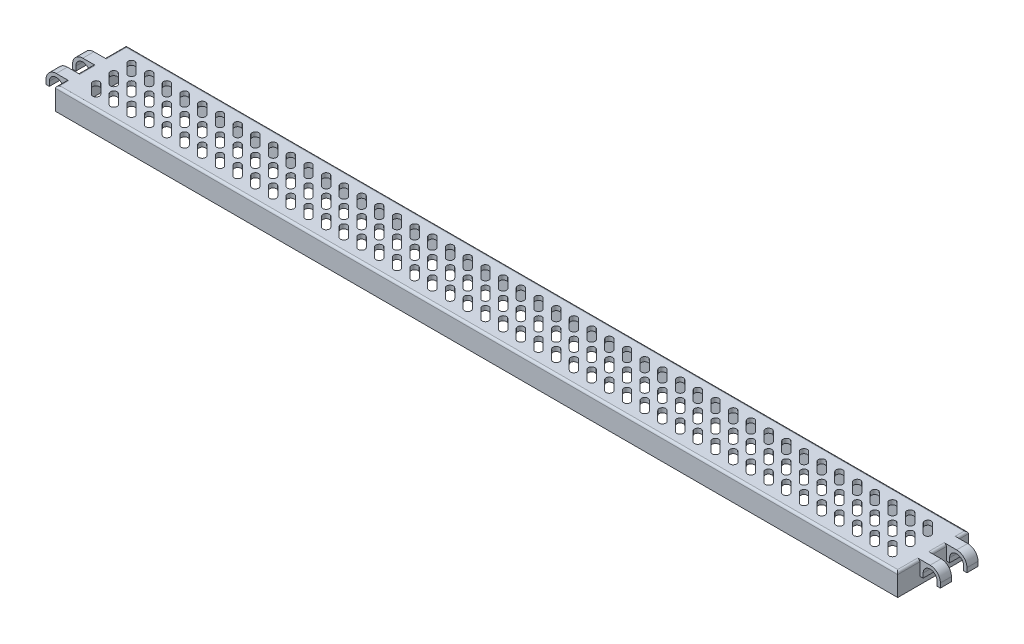
SolidWorks part; units mm, degrees
ref_plane "Ebene vorne" through (0, 0, 0) normal (0, 0, 1) x (1, 0, 0)
ref_plane "Ebene oben" through (0, 0, 0) normal (0, 1, 0) x (1, 0, 0)
ref_plane "Ebene rechts" through (0, 0, 0) normal (1, 0, 0) x (0, 0, -1)
sketch "Skizze1" plane through (0, 0, 0) normal (0, 0, 1) x (1, 0, 0)
  line L0 (-195, 0) -> (195, 0) construction
  line L1 (-198.15, 0) -> (-198.15, -2)
  line L2 (-191.85, 0) -> (-191.85, -2)
  line L3 (-190.35, -5.35) -> (190.35, -5.35)
  line L4 (-198.15, -2) -> (-199.65, -2)
  line L5 (-199.65, -2) -> (-199.65, 0)
  line L6 (-195, 4.65) -> (195, 4.65)
  line L7 (0, 4.65) -> (0, -5.35) construction
  line L8 (-191.85, -2) -> (-190.35, -2)
  line L9 (-190.35, -2) -> (-190.35, -5.35)
  line L10 (190.35, -2) -> (190.35, -5.35)
  line L11 (191.85, -2) -> (190.35, -2)
  line L12 (199.65, -2) -> (199.65, 0)
  line L13 (198.15, -2) -> (199.65, -2)
  line L14 (191.85, 0) -> (191.85, -2)
  line L15 (198.15, 0) -> (198.15, -2)
  arc A0 (-198.15, 0) -> (-191.85, 0) centre (-195, 0) cw
  arc A1 (-199.65, 0) -> (-195, 4.65) centre (-195, 0) cw
  arc A2 (199.65, 0) -> (195, 4.65) centre (195, 0) ccw
  arc A3 (198.15, 0) -> (191.85, 0) centre (195, 0) ccw
  point P3 (0, 0)
  dimension "D2" = 3.15
  dimension "D1" = 390
  dimension "D3" = 1.5
  dimension "D4" = 2
  dimension "D5" = 10
extrude "Aufsatz-Linear austragen2" add sketch "Skizze1" along normal mid plane 32
sketch "Skizze3" plane through (0, -5.35, 0) normal (0, -1, 0) x (1, 0, 0)
  line L0 (-190.35, 16) -> (-190.35, -16) construction
  line L1 (-199.65, 16) -> (-190.35, 16)
  line L2 (-199.65, 16) -> (-199.65, 11)
  line L3 (-199.65, 11) -> (-190.35, 11)
  line L4 (-190.35, 16) -> (-190.35, 11)
  line L5 (-199.65, 16) -> (-199.65, -16) construction
  line L6 (-199.65, 6) -> (-190.35, 6)
  line L7 (-199.65, 6) -> (-199.65, -1)
  line L8 (-199.65, -1) -> (-190.35, -1)
  line L9 (-190.35, 6) -> (-190.35, -1)
  line L10 (-190.35, 16) -> (-190.35, -16) construction
  line L11 (199.65, 16) -> (199.65, -16) construction
  line L12 (-199.65, -16) -> (-190.35, -16)
  line L13 (-199.65, -16) -> (-199.65, -6)
  line L14 (-199.65, -6) -> (-190.35, -6)
  line L15 (-190.35, -16) -> (-190.35, -6)
  line L16 (190.35, 16) -> (199.65, 16)
  line L17 (190.35, 16) -> (190.35, 6)
  line L18 (190.35, 6) -> (199.65, 6)
  line L19 (199.65, 16) -> (199.65, 6)
  line L20 (190.35, 16) -> (190.35, -16) construction
  line L21 (190.35, 1) -> (199.65, 1)
  line L22 (190.35, 1) -> (190.35, -6)
  line L23 (190.35, -6) -> (199.65, -6)
  line L24 (199.65, 1) -> (199.65, -6)
  line L26 (190.35, -11) -> (199.65, -11)
  line L27 (190.35, -11) -> (190.35, -16)
  line L28 (190.35, -16) -> (199.65, -16)
  line L29 (199.65, -11) -> (199.65, -16)
  point P38 (195, -6)
  dimension "D1" = 5
  dimension "D2" = 5
  dimension "D3" = 5
  dimension "D4" = 10
  dimension "D5" = 5
  dimension "D6" = 5
extrude "Schnitt-Linear austragen1" cut sketch "Skizze3" against normal through all
sketch "Skizze4" plane through (0, -5.35, 0) normal (0, -1, 0) x (1, 0, 0)
  line L8 (-187.35, -13) -> (187.35, -13)
  line L9 (187.35, -13) -> (187.35, 13)
  line L10 (187.35, 13) -> (-187.35, 13)
  line L11 (-187.35, 13) -> (-187.35, -13)
  line L12 (-187.35, -13) -> (187.35, -13)
  line L13 (187.35, -13) -> (187.35, 13)
  line L14 (187.35, 13) -> (-187.35, 13)
  line L15 (-187.35, 13) -> (-187.35, -13)
  dimension "D1" = 3
extrude "Schnitt-Linear austragen2" cut sketch "Skizze4" against normal offset from surface (8 mm away) 2 up to face at (0, 4.65, 0)
sketch "Skizze5" plane through (0, 2.65, 0) normal (0, -1, 0) x (1, 0, 0)
  line L0 (-187.35, -13) -> (187.35, -13) construction
  line L1 (-182.1, -10.1) -> (-177.8574, -5.8574) construction
  line L2 (-183.1607, -9.0393) -> (-178.918, -4.7967)
  line L3 (-181.0393, -11.1607) -> (-176.7967, -6.918)
  line L4 (187.35, -13) -> (-187.35, -13) construction
  line L5 (-187.35, -13) -> (-187.35, 13) construction
  arc A0 (-183.1607, -9.0393) -> (-181.0393, -11.1607) centre (-182.1, -10.1) ccw
  arc A1 (-176.7967, -6.918) -> (-178.918, -4.7967) centre (-177.8574, -5.8574) ccw
  point P4 (-179.9787, -7.9787)
  point P11 (-183.3039, -15.5)
  dimension "D3" = 9
  dimension "D4" = 1.4
  dimension "D5" = 3.75
  dimension "D1" = 45
  dimension "D2" = 3
extrude "Schnitt-Linear austragen3" cut sketch "Skizze5" against normal through all
pattern_linear "Lineares Muster1" count 46 spacing 8 along (1, 0, 0) count 3 spacing 8 along (0, 0, 1) of "Schnitt-Linear austragen3"
fillet "Verrundung1" radius 1 8 edges at (-190.35, 4.65, 13.5) (-190.35, 4.65, 2.5) (-190.35, 4.65, -11) (0, 4.65, 16) (190.35, 4.65, 11) (190.35, 4.65, -2.5) (0, 4.65, -16) (190.35, 4.65, -13.5)
